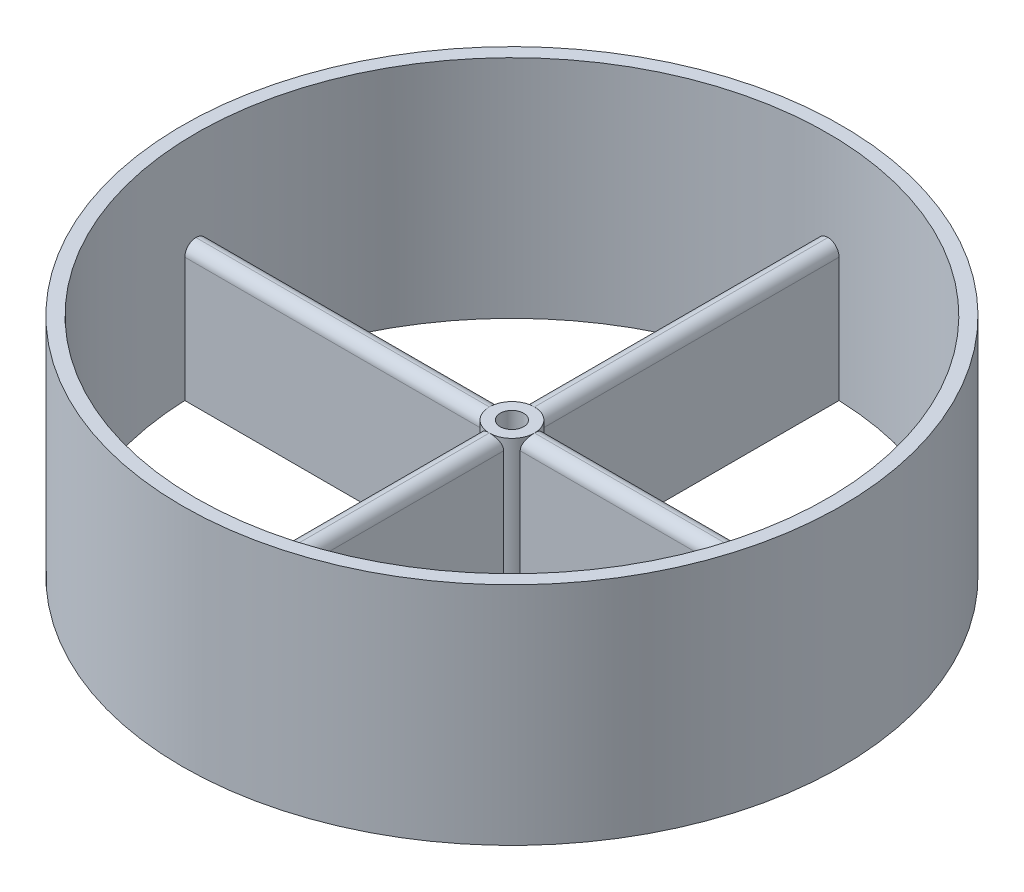
SolidWorks part; units mm, degrees
ref_plane "Front Plane" through (0, 0, 0) normal (0, 0, 1) x (1, 0, 0)
ref_plane "Top Plane" through (0, 0, 0) normal (0, 1, 0) x (1, 0, 0)
ref_plane "Right Plane" through (0, 0, 0) normal (1, 0, 0) x (0, 0, -1)
sketch "Sketch1" plane through (0, 0, 0) normal (0, 1, 0) x (1, 0, 0)
  line L1 (-2.5, 4.3301) -> (-2.5, 69.9553)
  line L6 (0.7141, -2.5) -> (-0.7141, -2.5)
  line L11 (96.0457, -5) -> (96.12, -5)
  line L16 (2.5, 4.3301) -> (2.5, 69.9553)
  line L17 (4.3301, 2.5) -> (69.9553, 2.5)
  line L18 (4.3301, -2.5) -> (69.9553, -2.5)
  line L19 (2.5, -4.3301) -> (2.5, -69.9553)
  line L20 (-2.5, -4.3301) -> (-2.5, -69.9553)
  line L21 (-4.3301, 2.5) -> (-69.9553, 2.5)
  line L22 (-4.3301, -2.5) -> (-69.9553, -2.5)
  circle A0 centre (0, 0) radius 2.6
  arc A1 (-2.5, 4.3301) -> (-4.3301, 2.5) centre (0, 0) ccw
  arc A2 (69.9553, 2.5) -> (2.5, 69.9553) centre (0, 0) ccw
  arc A3 (2.5, -69.9553) -> (69.9553, -2.5) centre (0, 0) ccw
  arc A4 (-69.9553, -2.5) -> (-2.5, -69.9553) centre (0, 0) ccw
  arc A5 (-4.3301, -2.5) -> (-2.5, -4.3301) centre (0, 0) ccw
  arc A6 (2.5, -4.3301) -> (4.3301, -2.5) centre (0, 0) ccw
  arc A7 (4.3301, 2.5) -> (2.5, 4.3301) centre (0, 0) ccw
  arc A10 (-2.5, 69.9553) -> (-69.9553, 2.5) centre (0, 0) ccw
  circle A11 centre (0, 0) radius 73
extrude "Boss-Extrude1" add sketch "Sketch1" along normal blind 50 contours A11 L17 A7 L16 A2 L19 A6 L18 A3 L22 A5 L20 A4 A0 A10 L1 A1 L21 region at (-70.9352, 0, 0)
sketch "Sketch2" plane through (0, 50, 0) normal (0, 1, 0) x (1, 0, 0)
  circle A0 centre (0, 0) radius 70
extrude "Cut-Extrude1" cut sketch "Sketch2" against normal blind 20
fillet "Fillet1" radius 2.5 1 edges at (2.5, 30, -37.1427)
fillet "Fillet2" radius 2.5 7 edges at (37.1427, 30, -2.5) (37.1427, 30, 2.5) (2.5, 30, 37.1427) (-2.5, 30, 37.1427) (-37.1427, 30, 2.5) (-37.1427, 30, -2.5) (-2.5, 30, -37.1427)
